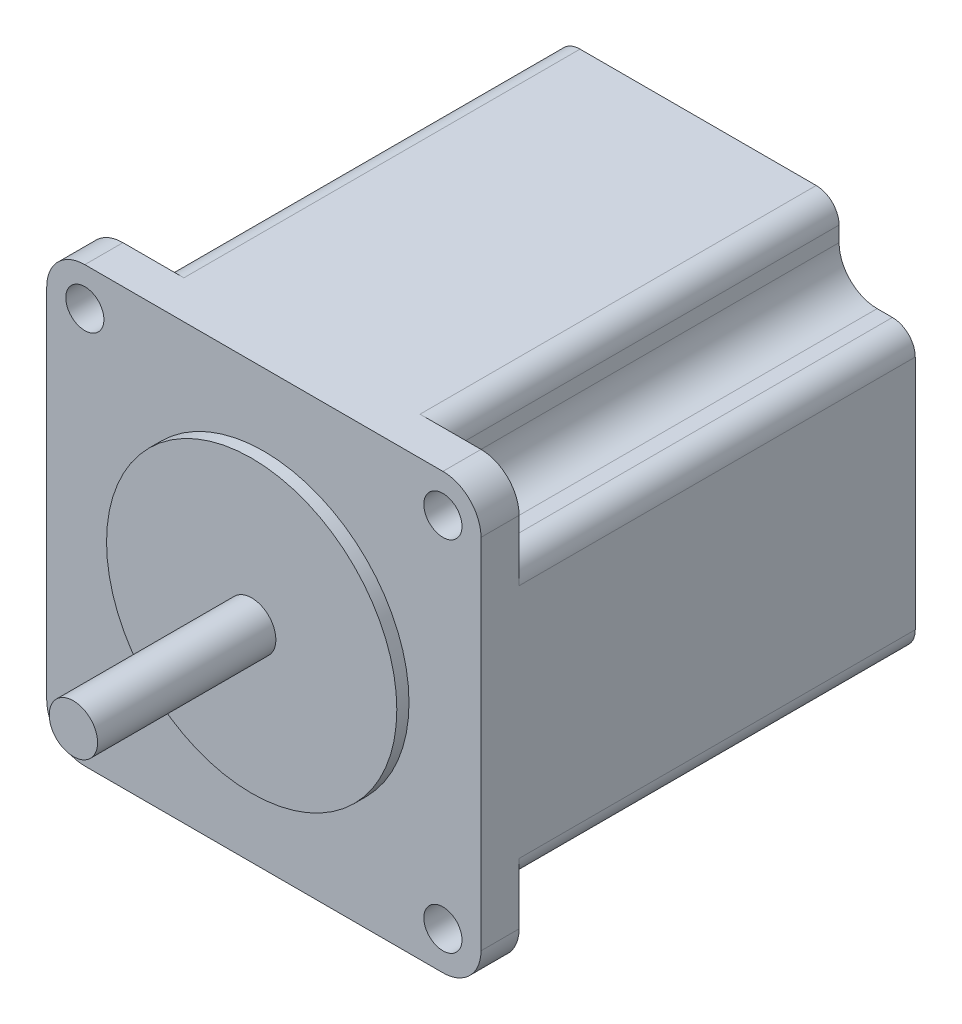
SolidWorks part; units mm, degrees
ref_plane "Front Plane" through (0, 0, 0) normal (0, 0, 1) x (1, 0, 0)
ref_plane "Top Plane" through (0, 0, 0) normal (0, 1, 0) x (1, 0, 0)
ref_plane "Right Plane" through (0, 0, 0) normal (1, 0, 0) x (0, 0, -1)
sketch "Sketch1" plane through (0, 0, 0) normal (0, 0, 1) x (1, 0, 0)
  line L1 (-23.5, -28.5) -> (23.5, -28.5)
  line L2 (-28.5, -23.5) -> (-28.5, 23.5)
  line L3 (-23.5, 28.5) -> (23.5, 28.5)
  line L4 (28.5, -23.5) -> (28.5, 23.5)
  line L5 (-28.5, -28.5) -> (28.5, 28.5) construction
  line L6 (-28.5, 28.5) -> (28.5, -28.5) construction
  line L7 (-23.57, -23.57) -> (23.57, -23.57) construction
  line L8 (-23.57, -23.57) -> (-23.57, 23.57) construction
  line L9 (-23.57, 23.57) -> (23.57, 23.57) construction
  line L10 (23.57, -23.57) -> (23.57, 23.57) construction
  line L11 (-23.57, -23.57) -> (23.57, 23.57) construction
  line L12 (-23.57, 23.57) -> (23.57, -23.57) construction
  arc A0 (-23.5, -28.5) -> (-28.5, -23.5) centre (-23.5, -23.5) cw
  arc A1 (23.5, -28.5) -> (28.5, -23.5) centre (23.5, -23.5) ccw
  arc A2 (23.5, 28.5) -> (28.5, 23.5) centre (23.5, 23.5) cw
  arc A3 (-23.5, 28.5) -> (-28.5, 23.5) centre (-23.5, 23.5) ccw
  circle A4 centre (-23.5, 23.5) radius 2.5
  circle A5 centre (23.5, 23.5) radius 2.5
  circle A6 centre (23.5, -23.5) radius 2.5
  circle A7 centre (-23.57, -23.57) radius 2.5
  point P0 (0, 0)
  point P18 (0, 0)
  dimension "D3" = 5
  dimension "D6" = 5
  dimension "D7" = 5
  dimension "D8" = 5
  dimension "D9" = 5
  dimension "D1" = 57
  dimension "D2" = 57
  dimension "D4" = 47.14
  dimension "D5" = 47.14
extrude "Boss-Extrude1" add sketch "Sketch1" along normal mid plane 5
sketch "Sketch2" plane through (0, 0, 2.5) normal (0, 0, 1) x (1, 0, 0)
  circle A0 centre (0, 0) radius 3.175
  dimension "D1" = 6.35
extrude "Boss-Extrude2" add sketch "Sketch2" along normal blind 25
sketch "Sketch3" plane through (0, 0, 2.5) normal (0, 0, 1) x (1, 0, 0)
  circle A0 centre (0, 0) radius 19.05
  dimension "D1" = 38.1
extrude "Boss-Extrude3" add sketch "Sketch3" along normal blind 1.6
sketch "Sketch4" plane through (0, 0, -2.5) normal (0, 0, -1) x (-1, 0, 0)
  line L0 (-18.5, 23.5) -> (-18.5, 25.5)
  line L1 (-23.5, 28.5) -> (23.5, 28.5) construction
  line L2 (-15.5, 28.5) -> (15.5, 28.5)
  line L3 (18.5, 25.5) -> (18.5, 23.5)
  line L4 (23.5, 18.5) -> (25.5, 18.5)
  line L5 (28.5, 23.5) -> (28.5, -23.5) construction
  line L6 (28.5, 15.5) -> (28.5, -15.57)
  line L7 (25.5, -18.57) -> (23.57, -18.57)
  line L8 (18.57, -23.57) -> (18.57, -25.5)
  line L9 (23.5, -28.5) -> (-23.5, -28.5) construction
  line L10 (15.57, -28.5) -> (-15.5, -28.5)
  line L11 (-18.5, -25.5) -> (-18.5, -23.5)
  line L12 (-23.5, -18.5) -> (-25.5, -18.5)
  line L13 (-28.5, -23.5) -> (-28.5, 23.5) construction
  line L14 (-28.5, -15.5) -> (-28.5, 15.5)
  line L15 (-25.5, 18.5) -> (-23.5, 18.5)
  arc A0 (-23.5, 18.5) -> (-18.5, 23.5) centre (-23.5, 23.5) ccw
  arc A1 (18.5, 23.5) -> (23.5, 18.5) centre (23.5, 23.5) ccw
  arc A2 (23.57, -18.57) -> (18.57, -23.57) centre (23.57, -23.57) ccw
  arc A3 (-18.5, -23.5) -> (-23.5, -18.5) centre (-23.5, -23.5) ccw
  arc A4 (-28.5, 15.5) -> (-25.5, 18.5) centre (-25.5, 15.5) cw
  arc A5 (-18.5, 25.5) -> (-15.5, 28.5) centre (-15.5, 25.5) cw
  arc A6 (15.5, 28.5) -> (18.5, 25.5) centre (15.5, 25.5) cw
  arc A7 (28.5, 15.5) -> (25.5, 18.5) centre (25.5, 15.5) ccw
  arc A8 (28.5, -15.57) -> (25.5, -18.57) centre (25.5, -15.57) cw
  arc A9 (15.57, -28.5) -> (18.57, -25.5) centre (15.57, -25.5) ccw
  arc A10 (-15.5, -28.5) -> (-18.5, -25.5) centre (-15.5, -25.5) cw
  arc A11 (-25.5, -18.5) -> (-28.5, -15.5) centre (-25.5, -15.5) cw
  point P7 (-28.5, 18.5)
  point P37 (-18.5, 28.5)
  point P40 (18.5, 28.5)
  point P43 (28.5, 18.5)
  point P46 (28.5, -18.57)
  point P49 (18.57, -28.5)
  point P52 (-18.5, -28.5)
  point P55 (-28.5, -18.5)
  dimension "D1" = 10
  dimension "D2" = 10
  dimension "D3" = 10
  dimension "D4" = 10
  dimension "D5" = 3
extrude "Boss-Extrude4" add sketch "Sketch4" along normal blind 52
